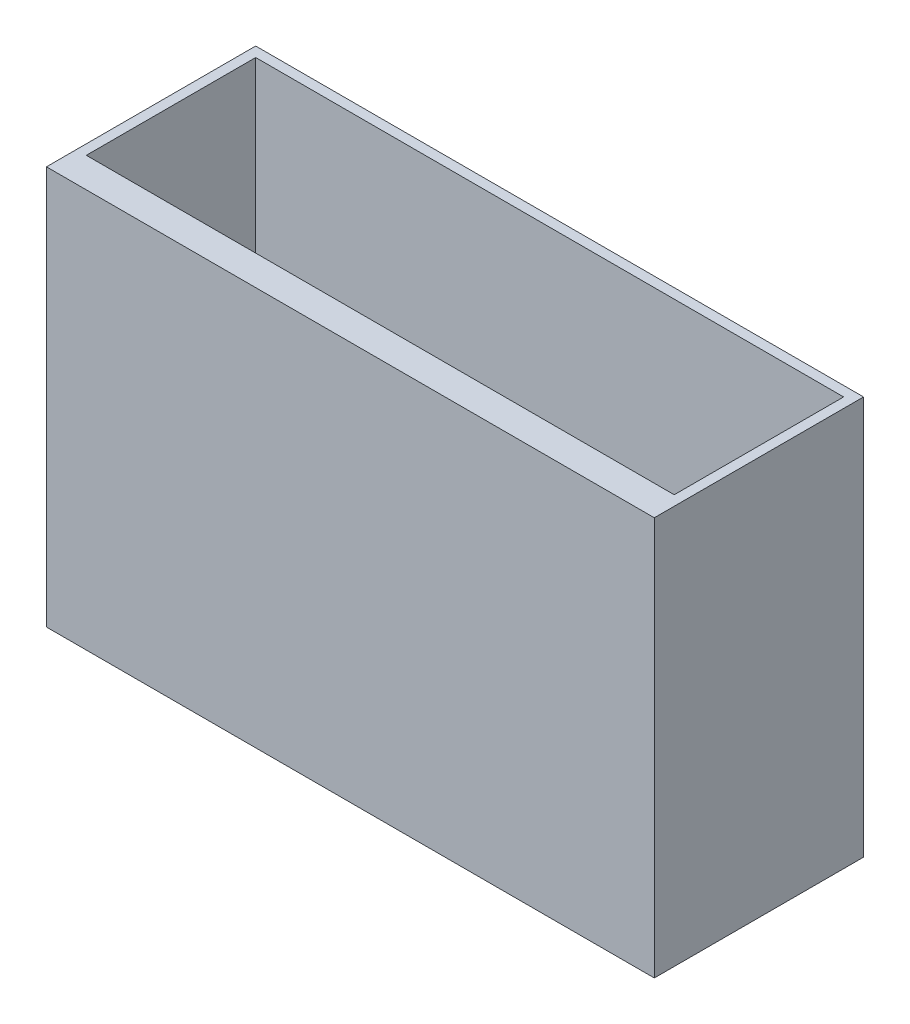
SolidWorks part; units mm, degrees
ref_plane "Front Plane" through (0, 0, 0) normal (0, 0, 1) x (1, 0, 0)
ref_plane "Top Plane" through (0, 0, 0) normal (0, 1, 0) x (1, 0, 0)
ref_plane "Right Plane" through (0, 0, 0) normal (1, 0, 0) x (0, 0, -1)
sketch "Sketch1" plane through (0, 0, 0) normal (0, 1, 0) x (1, 0, 0)
  line L0 (-14.75, 4.25) -> (-15.25, 4.25) construction
  line L1 (-14.75, 4.25) -> (14.75, 4.25)
  line L2 (-14.75, 4.25) -> (-14.75, -4.25)
  line L3 (-14.75, -4.25) -> (14.75, -4.25)
  line L4 (14.75, 4.25) -> (14.75, -4.25)
  line L5 (-14.75, 4.25) -> (14.75, -4.25) construction
  line L6 (-14.75, -4.25) -> (14.75, 4.25) construction
  line L7 (15.25, 4.75) -> (-15.25, 4.75)
  line L8 (15.25, 4.75) -> (15.25, -4.75)
  line L9 (15.25, -4.75) -> (-15.25, -4.75)
  line L10 (-15.25, 4.75) -> (-15.25, -4.75)
  line L11 (15.25, 4.75) -> (-15.25, -4.75) construction
  line L12 (15.25, -4.75) -> (-15.25, 4.75) construction
  line L13 (-14.75, 4.25) -> (-14.75, 4.75) construction
  line L15 (-15.25, -5.75) -> (15.25, -5.75)
  line L16 (-15.25, -5.75) -> (-15.25, -4.75)
  line L17 (-15.25, -4.75) -> (15.25, -4.75)
  line L18 (15.25, -5.75) -> (15.25, -4.75)
  point P0 (0, 0)
  point P6 (0, 0)
  dimension "D1" = 29.5
  dimension "D2" = 8.5
  dimension "D3" = 0.5
  dimension "D4" = 1
extrude "Boss-Extrude1" add sketch "Sketch1" along normal blind 20 contours L7 L10 L9 L8 L1 L4 L3 L2 | L15 L18 L9 L16 region at (14.9305, 0, 0) region at (0, 0, 5.25)
